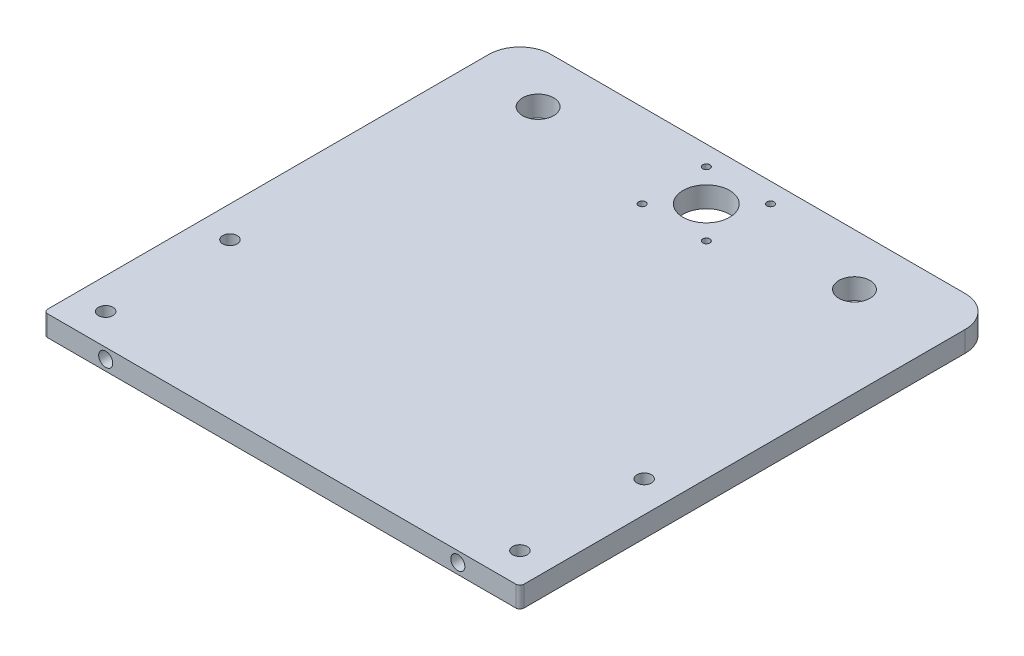
SolidWorks part; units mm, degrees
ref_plane "Vorne" through (0, 0, 0) normal (0, 0, 1) x (1, 0, 0)
ref_plane "Oben" through (0, 0, 0) normal (0, 1, 0) x (1, 0, 0)
ref_plane "Rechts" through (0, 0, 0) normal (1, 0, 0) x (0, 0, -1)
ref_plane "E_Boden" through (0, 1, 0) normal (0, 1, 0) x (1, 0, 0)
sketch "Skizze1" plane through (0, 0, 0) normal (0, 1, 0) x (1, 0, 0)
  line L0 (-170.1685, 0) -> (216.6498, 0) construction
  line L1 (0, 0) -> (0, 128.6817) construction
  line L2 (0, 128.6817) -> (0, -115.148) construction
  line L4 (-115, 115) -> (115, 115)
  line L5 (-115, 115) -> (-115, -115)
  line L6 (-115, -115) -> (115, -115)
  line L7 (115, 115) -> (115, -115)
  dimension "D1" = 230
  dimension "D2" = 230
extrude "Aufsatz-Linear austragen1" add sketch "Skizze1" along normal blind 10
hole_wizard "Ø15.0 (15) Durchmesser Bohrung1" positions "Skizze6" profile "Skizze7" hole size "Ø15.0" standard "DIN" end condition through all
sketch "Skizze6" plane through (0, 10, 0) normal (0, 1, 0) x (1, 0, 0)
  line L1 (115, 115) -> (-115, 115) construction
  point P0 (-81.223, 90)
  point P2 (71.5255, 90)
  dimension "D1" = 25
  dimension "D2" = 25
sketch "Skizze7" plane through (-81.223, 10, -90) normal (1, 0, 0) x (0, 0, 1)
  line L0 (0, 0) -> (0, 10)
  line L1 (0, 10) -> (7.5, 10)
  line L2 (7.5, 10) -> (7.5, 0)
  line L5 (7.5, 0) -> (0, 0)
  line L11 (0, -6.35) -> (0, 107.95) construction
  dimension "Bohrerdurchmesser" = 15
  dimension "Bohrungstiefe" = 10
hole_wizard "Ø3.4 (3.4) Durchmesser Bohrung1" positions "Skizze8" profile "Skizze9" hole size "Ø3.4" standard "DIN" end condition through all
sketch "Skizze8" plane through (0, 10, 0) normal (0, 1, 0) x (1, 0, 0)
  line L0 (115, 115) -> (-115, 115) construction
  line L1 (0, 71.4415) -> (0, 3.4399) construction
  line L3 (-115, 115) -> (-115, -115) construction
  line L4 (-44.1401, 90) -> (32.4162, 90) construction
  point P0 (-15.5, 105.5)
  point P2 (15.5, 105.5)
  point P4 (-15.5, 74.5)
  point P6 (15.5, 74.5)
  point P32 (-15.5, 105.5)
  dimension "D2" = 31
  dimension "D3" = 31
  dimension "D4" = 115
  dimension "D5" = 25
sketch "Skizze9" plane through (-15.5, 10, -105.5) normal (1, 0, 0) x (0, 0, 1)
  line L0 (0, 0) -> (0, 10)
  line L1 (0, 10) -> (1.725, 10)
  line L2 (1.7, 9.975) -> (1.7, 0.025)
  line L3 (1.7, 0.025) -> (1.725, 0)
  line L5 (1.725, 0) -> (0, 0)
  line L6 (-1.7, 0.025) -> (-1.725, 0) construction
  line L7 (1.725, 10) -> (1.7, 9.975)
  line L8 (-1.725, 10) -> (-1.7, 9.975) construction
  line L11 (0, -6.35) -> (0, 107.95) construction
  dimension "Bohrerdurchmesser" = 3.4
  dimension "Bohrungstiefe" = 10
  dimension "Senkdurchmesser2 (Oben)" = 3.45
  dimension "Senkwinkel2 (Oben)" = 90
  dimension "Senkdurchmesser2 (Unten)" = 3.45
  dimension "Senkwinkel2 (Unten)" = 90
hole_wizard "Ø22.5 (22.5) Durchmesser Bohrung1" positions "Skizze10" profile "Skizze11" hole size "Ø22.5" standard "DIN" end condition through all
sketch "Skizze10" plane through (0, 10, 0) normal (0, 1, 0) x (1, 0, 0)
  line L0 (115, 115) -> (-115, 115) construction
  point P0 (0, 90)
  dimension "D1" = 25
sketch "Skizze11" plane through (0, 10, -90) normal (1, 0, 0) x (0, 0, 1)
  line L0 (0, 0) -> (0, 10)
  line L1 (0, 10) -> (11.25, 10)
  line L2 (11.25, 10) -> (11.25, 0)
  line L5 (11.25, 0) -> (0, 0)
  line L11 (0, -6.35) -> (0, 107.95) construction
  dimension "Bohrerdurchmesser" = 22.5
  dimension "Bohrungstiefe" = 10
hole_wizard "Ø7.0 (7) Durchmesser Bohrung1" positions "Skizze12" profile "Skizze13" hole size "Ø7.0" standard "DIN" end condition through all
sketch "Skizze12" plane through (0, 10, 0) normal (0, 1, 0) x (1, 0, 0)
  line L0 (-115, 115) -> (-115, -115) construction
  line L1 (115, -115) -> (115, 115) construction
  line L2 (-115, -115) -> (115, -115) construction
  point P0 (-100, -40)
  point P2 (-100, -100)
  point P4 (100, -40)
  point P6 (100, -100)
  dimension "D1" = 15
  dimension "D2" = 15
  dimension "D3" = 15
  dimension "D4" = 60
sketch "Skizze13" plane through (-100, 10, 40) normal (1, 0, 0) x (0, 0, 1)
  line L0 (0, 0) -> (0, 10)
  line L1 (0, 10) -> (3.5, 10)
  line L2 (3.5, 10) -> (3.5, 0)
  line L5 (3.5, 0) -> (0, 0)
  line L11 (0, -6.35) -> (0, 107.95) construction
  dimension "Bohrerdurchmesser" = 7
  dimension "Bohrungstiefe" = 10
fillet "Verrundung5" radius 15 2 edges at (115, 5, -115) (-115, 5, -115)
fillet "Verrundung6" radius 2 2 edges at (115, 5, 115) (-115, 5, 115)
hole_wizard "M8 Gewindebohrung1" positions "Skizze16" profile "Skizze17" tap size "M8" standard "DIN"
sketch "Skizze16" plane through (0, 0, 115) normal (0, 0, 1) x (1, 0, 0)
  line L0 (0, -9.8322) -> (0, 40.9109) construction
  line L5 (-132.4013, 5) -> (137.634, 5) construction
  line L7 (-113, 10) -> (113, 10) construction
  line L8 (-113, 0) -> (113, 0) construction
  point P0 (-85, 5)
  point P2 (85, 5)
  dimension "D1" = 170
sketch "Skizze17" plane through (-85, 5, 115) normal (1, 0, 0) x (0, -1, 0)
  line L0 (0, 0) -> (0, 32.0429)
  line L1 (0, 32.0429) -> (3.4, 30)
  line L2 (3.4, 30) -> (3.4, 0)
  line L5 (3.4, 0) -> (0, 0)
  line L10 (0, 32.0429) -> (-3.4, 30) construction
  line L11 (0, -6.35) -> (0, 107.95) construction
  dimension "Bohrerdurchmesser" = 6.8
  dimension "Bohrungstiefe" = 30
  dimension "Spitzenwinkel" = 118
cosmetic thread "Bohrungsgewinde1" parameters "D1"=16, "D2"=8
cosmetic thread "Bohrungsgewinde2" parameters "D1"=16, "D2"=8
